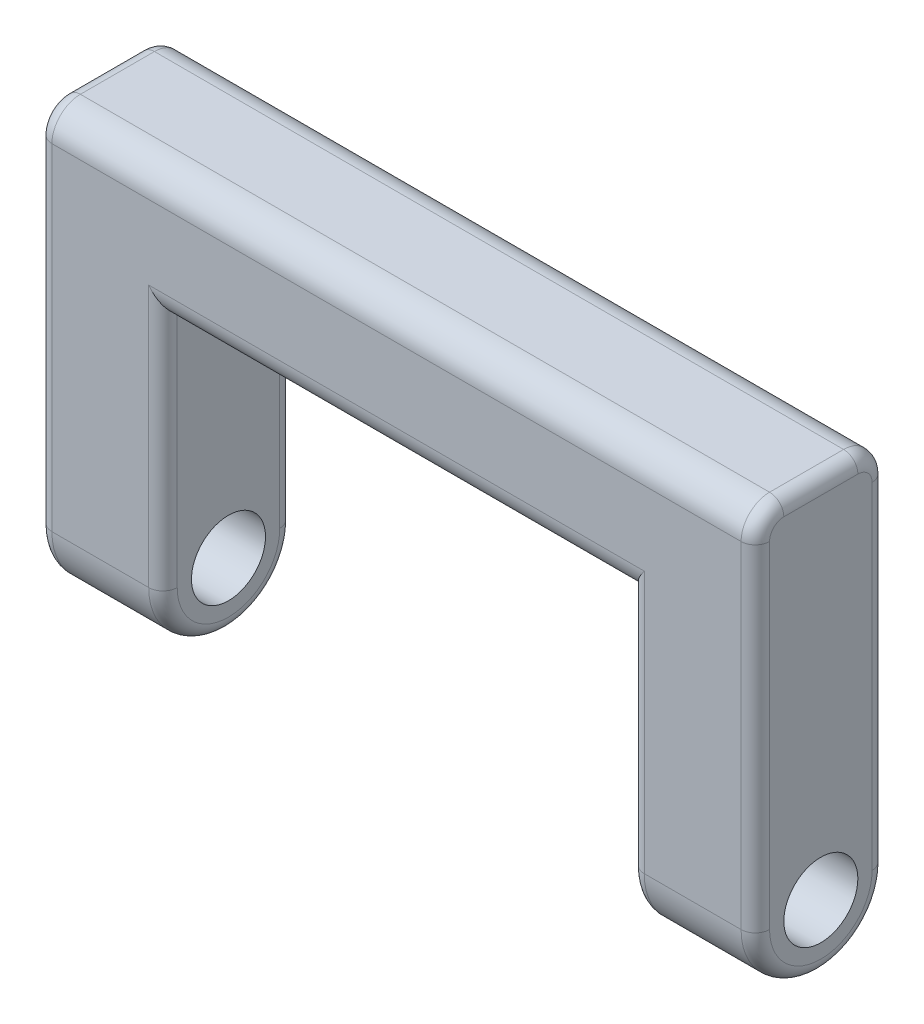
SolidWorks part; units mm, degrees
ref_plane "Front Plane" through (0, 0, 0) normal (0, 0, 1) x (1, 0, 0)
ref_plane "Top Plane" through (0, 0, 0) normal (0, 1, 0) x (1, 0, 0)
ref_plane "Right Plane" through (0, 0, 0) normal (1, 0, 0) x (0, 0, -1)
sketch "Sketch1" plane through (0, 0, 0) normal (1, 0, 0) x (0, 0, -1)
  line L0 (-11.5, 11.5) -> (11.5, 11.5) construction
  line L1 (-11.5, -12.5) -> (11.5, -12.5)
  line L2 (-11.5, -12.5) -> (-11.5, 59)
  line L3 (-6.5, 64) -> (6.5, 64)
  line L4 (11.5, -12.5) -> (11.5, 59)
  line L5 (-11.5, -12.5) -> (11.5, 64) construction
  line L6 (-11.5, 64) -> (11.5, -12.5) construction
  line L7 (-11.5, 64) -> (11.5, 64)
  line L8 (-11.5, 64) -> (-11.5, 46)
  line L9 (-6.5, 41) -> (6.5, 41)
  line L10 (11.5, 64) -> (11.5, 46)
  circle A0 centre (0, 0) radius 6.5
  circle A1 centre (0, 0) radius 11.5
  arc A2 (-11.5, 46) -> (-6.5, 41) centre (-6.5, 46) ccw
  arc A3 (6.5, 41) -> (11.5, 46) centre (6.5, 46) ccw
  arc A4 (6.5, 64) -> (11.5, 59) centre (6.5, 59) cw
  arc A5 (-11.5, 59) -> (-6.5, 64) centre (-6.5, 59) cw
  point P3 (0, 25.75)
  point P16 (11.5, 41)
  dimension "D1" = 13
  dimension "D6" = 5
  dimension "D2" = 23
  dimension "D3" = 41
  dimension "D4" = 12.5
  dimension "D5" = 23
extrude "Boss-Extrude1" add sketch "Sketch1" against normal blind 22 contours A1 A0 | A3 L9 A2 L2 A1 L4 | A5 L2 A2 L9 A3 L4 A4 L3 region at (0, 25.1604, 0) region at (0, 11.1747, 0) region at (0, 52.5, 0)
extrude "Boss-Extrude3" add sketch "Sketch1<4>" along normal blind 82 contours A5 L2 A2 L9 A3 L4 A4 L3 region at (0, 52.5, 0)
sketch "Sketch1<4>" plane through (0, 0, 0) normal (1, 0, 0) x (0, 0, -1) same geometry as "Sketch1"
fillet "Fillet3" radius 2.5 9 edges at (-22, -11.5, 0) (-22, 29.5, 11.5) (-22, 62.5355, 10.0355) (-22, 64, 0) (-22, 62.5355, -10.0355) (-22, 29.5, -11.5) (0, 23, -11.5) (0, -11.5, 0) (0, 23, 11.5)
sketch "Sketch3" plane through (0, 41, 0) normal (0, -1, 0) x (1, 0, 0)
  line L0 (0, -6.5) -> (82, 6.5) construction
  line L1 (41, -6.5) -> (41, 6.5) construction
  line L2 (82, 6.5) -> (0, 6.5) construction
  point P9 (41, 0)
ref_plane "Plane2" through (41, 0, 0) normal (1, 0, 0) x (0, 0, -1)
mirror "Mirror1" about plane through (41, 0, 0) normal (1, 0, 0) of "Fillet3", "Boss-Extrude1"
